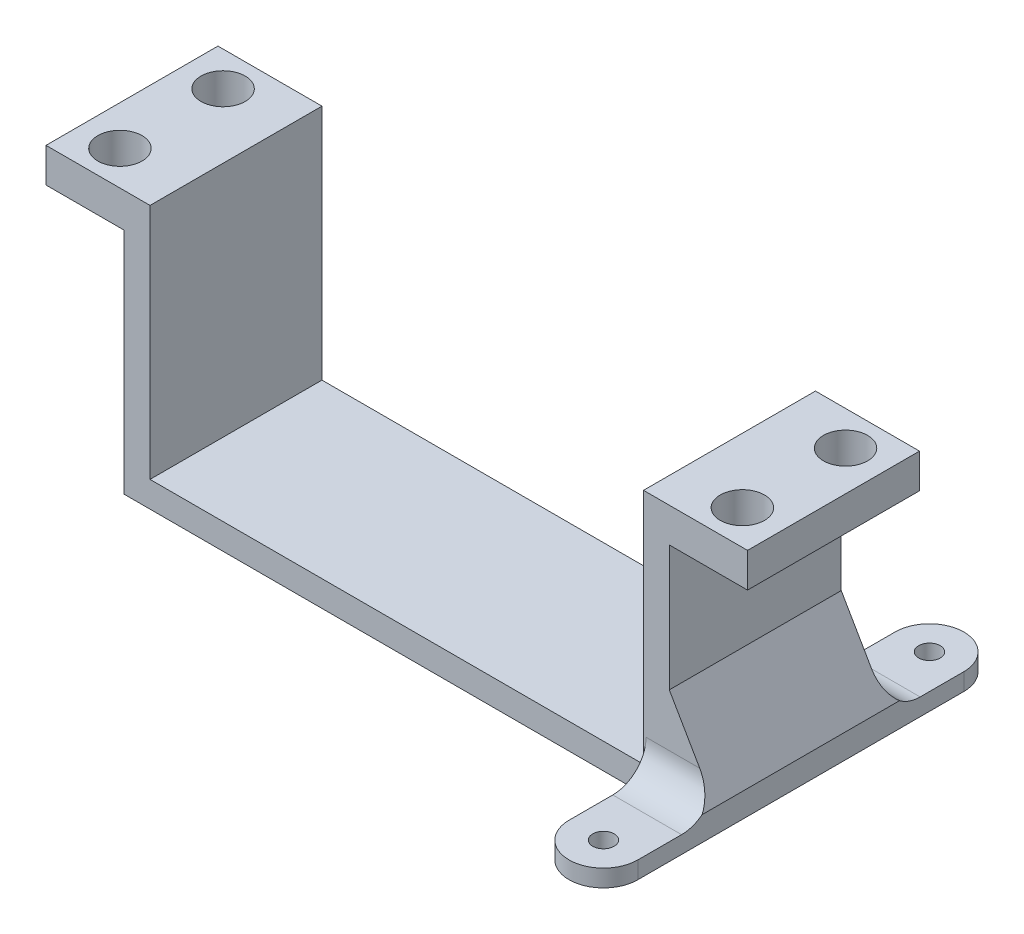
SolidWorks part; units mm, degrees
ref_plane "Front Plane" through (0, 0, 0) normal (0, 0, 1) x (1, 0, 0)
ref_plane "Top Plane" through (0, 0, 0) normal (0, 1, 0) x (1, 0, 0)
ref_plane "Right Plane" through (0, 0, 0) normal (1, 0, 0) x (0, 0, -1)
sketch "Sketch1" plane through (0, 0, 0) normal (0, 0, 1) x (1, 0, 0)
  line L0 (-3.81, 35.052) -> (0, 35.052)
  line L1 (0, 0) -> (72.898, 0)
  line L2 (0, 0) -> (0, 35.052)
  line L4 (72.898, 0) -> (72.898, 35.052)
  line L6 (-3.81, 35.052) -> (-3.81, -3.81)
  line L7 (-3.81, -3.81) -> (76.708, -3.81)
  line L8 (76.708, 35.052) -> (76.708, -3.81)
  line L9 (72.898, 35.052) -> (76.708, 35.052)
  dimension "D1" = 3.81
  dimension "D2" = 3.81
  dimension "D3" = 3.81
  dimension "D4" = 38.862
  dimension "D5" = 72.898
extrude "Boss-Extrude1" add sketch "Sketch1" along normal blind 25.4
sketch "Sketch2" plane through (0, -3.81, 0) normal (0, -1, 0) x (1, 0, 0)
  line L0 (78.359, 36.7792) -> (78.359, -11.3792) construction
  line L1 (76.708, 25.4) -> (76.708, 0) construction
  line L2 (73.279, 36.7792) -> (73.279, -11.3792)
  line L3 (83.439, 36.7792) -> (83.439, -11.3792)
  line L4 (-3.81, 25.4) -> (76.708, 25.4) construction
  circle A0 centre (78.359, 36.7792) radius 1.5875
  circle A1 centre (78.359, -11.3792) radius 1.5875
  arc A2 (83.439, 36.7792) -> (73.279, 36.7792) centre (78.359, 36.7792) ccw
  arc A3 (73.279, -11.3792) -> (83.439, -11.3792) centre (78.359, -11.3792) ccw
  point P4 (78.359, 12.7)
  point P5 (76.708, 12.7)
  point P6 (36.449, 25.4)
  point P9 (78.359, 35.1917)
  point P14 (78.359, -9.7917)
  dimension "D2" = 3.175
  dimension "D3" = 5.08
  dimension "D1" = 44.9834
  dimension "D4" = 41.91
extrude "Boss-Extrude2" add sketch "Sketch2" against normal blind 2.54
sketch "Sketch4" plane through (0, 35.052, 0) normal (0, 1, 0) x (1, 0, 0)
  line L0 (0, -25.4) -> (-3.81, -25.4) construction
  line L1 (0, 0) -> (-15.367, 0)
  line L2 (0, 0) -> (0, -25.4)
  line L3 (0, -25.4) -> (-15.367, -25.4)
  line L4 (-15.367, 0) -> (-15.367, -25.4)
  line L5 (-3.81, -25.4) -> (-3.81, 0) construction
  line L6 (-9.525, -5.08) -> (-9.525, -20.32) construction
  circle A0 centre (-9.525, -5.08) radius 3.2639
  circle A1 centre (-9.525, -20.32) radius 3.2639
  point P13 (-15.367, -12.7)
  point P14 (-9.525, -12.7)
  point P15 (0, 0)
  dimension "D1" = 6.5278
  dimension "D2" = 5.715
  dimension "D3" = 7.62
  dimension "D4" = 5.842
extrude "Boss-Extrude3" add sketch "Sketch4" against normal blind 5.08
ref_plane "Plane1" through (36.449, 0, 0) normal (1, 0, 0) x (0, 0, -1)
mirror "Mirror1" about plane through (36.449, 0, 0) normal (1, 0, 0) of "Boss-Extrude3"
chamfer "Chamfer1" distance 12.7 angle 30 1 edges at (76.708, -1.27, 12.7) first distance on face at (76.708, 14.351, 12.7)
fillet "Fillet1" radius 4.92 2 edges at (78.359, -1.27, 0) (78.359, -1.27, 25.4)
